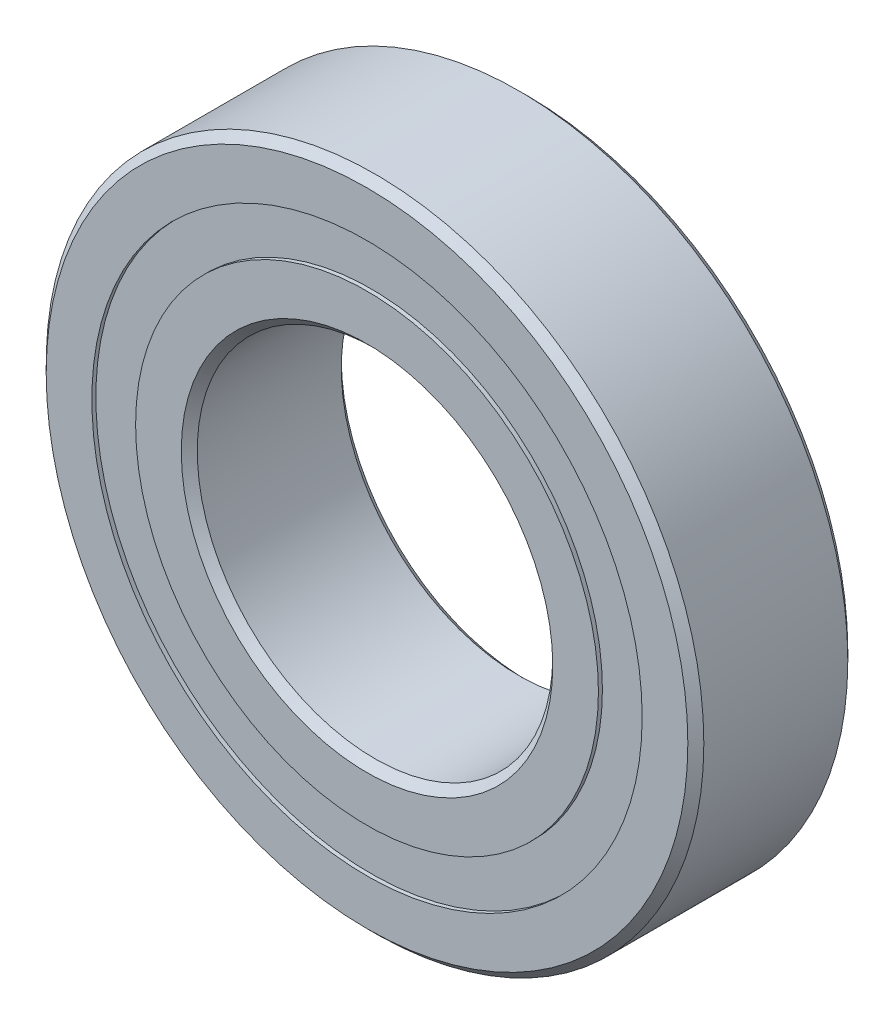
SolidWorks part; units mm, degrees
ref_plane "Front Plane" through (0, 0, 0) normal (0, 0, 1) x (1, 0, 0)
ref_plane "Top Plane" through (0, 0, 0) normal (0, 1, 0) x (1, 0, 0)
ref_plane "Right Plane" through (0, 0, 0) normal (1, 0, 0) x (0, 0, -1)
sketch "Sketch1" plane through (0, 0, 0) normal (1, 0, 0) x (0, 0, -1)
  line L0 (-4.5, 0) -> (4.5, 0) construction
  line L1 (0, 18.5) -> (0, -18.5) construction
  line L2 (4.05, 18.5) -> (-4.05, 18.5)
  line L3 (-4.05, 18.5) -> (-4.5, 18.05)
  line L4 (-4.5, 18.05) -> (-4.5, 15.4808)
  line L5 (-4.5, 15.4808) -> (-2, 15.4808)
  line L6 (4.5, 15.4808) -> (2, 15.4808)
  line L7 (4.5, 18.05) -> (4.5, 15.4808)
  line L8 (4.05, 18.5) -> (4.5, 18.05)
  line L9 (0, 18.5) -> (0, 14.25) construction
  line L10 (0, 14.25) -> (0, 10) construction
  arc A0 (-2, 15.4808) -> (2, 15.4808) centre (0, 14.25) cw
  point P14 (0, 10)
  dimension "Width" = 9
  dimension "OD" = 37
  dimension "D1" = 45
  dimension "D2" = 0.45
  dimension "Shaft Dia" = 20
  dimension "D3" = 4
  dimension "D4" = 1.2308
revolve "Revolve1" add sketch "Sketch1" angle 360 about L0
sketch "Sketch3" plane through (0, 0, 0) normal (1, 0, 0) x (0, 0, -1)
  line L0 (-4.5, 13.0192) -> (-2, 13.0192)
  line L1 (0, 18.5) -> (0, -18.5) construction
  line L2 (-4.5, 18.05) -> (-4.5, 15.4808) construction
  line L3 (-4.5, 13.0192) -> (-4.5, 10.45)
  line L4 (-4.05, 18.5) -> (-4.5, 18.05) construction
  line L5 (-4.5, 10.45) -> (-4.05, 10)
  line L6 (-4.05, 10) -> (4.05, 10)
  line L7 (4.05, 18.5) -> (4.05, -18.5) construction
  line L8 (4.05, 10) -> (4.5, 10.45)
  line L9 (4.5, -18.05) -> (4.5, 18.05) construction
  line L10 (4.5, 10.45) -> (4.5, 13.0192)
  line L11 (4.5, 13.0192) -> (2, 13.0192)
  line L13 (4.05, 18.5) -> (4.5, 18.05) construction
  arc A0 (2, 15.4808) -> (-2, 15.4808) centre (0, 14.25) ccw construction
  arc A1 (2, 13.0192) -> (-2, 13.0192) centre (0, 14.25) cw
revolve "Revolve3" add sketch "Sketch3" angle 360 about L0
sketch "Sketch4" plane through (0, 0, 0) normal (1, 0, 0) x (0, 0, -1)
  line L0 (-2.3484, 14.25) -> (2.3484, 14.25)
  arc A2 (-2.3484, 14.25) -> (2.3484, 14.25) centre (0, 14.25) cw
  arc A3 (2, 15.4808) -> (-2, 15.4808) centre (0, 14.25) ccw construction
revolve "Revolve4" add sketch "Sketch4" angle 360 about L0
ref_axis "Axis1" through (0, 0, -4.5) along (0, 0, 1)
pattern_circular "CirPattern1" count 12 every 30 about axis through (0, 0, -4.5) along (0, 0, 1) of bodies 104
sketch "Sketch5" plane through (0, 0, 0) normal (1, 0, 0) x (0, 0, -1)
  line L0 (-4.5, 15.4808) -> (-2, 15.4808) construction
  line L1 (-4.275, 15.4808) -> (-2.3484, 15.4808)
  line L2 (-4.275, 15.4808) -> (-4.275, 13.0192)
  line L3 (-4.275, 13.0192) -> (-2.3484, 13.0192)
  line L4 (-2.3484, 15.4808) -> (-2.3484, 13.0192)
  line L5 (-4.5, 13.0192) -> (-2, 13.0192) construction
  line L6 (4.5, 15.4808) -> (2, 15.4808) construction
  line L7 (4.275, 15.4808) -> (2.3484, 15.4808)
  line L8 (4.275, 15.4808) -> (4.275, 13.0192)
  line L9 (4.275, 13.0192) -> (2.3484, 13.0192)
  line L10 (2.3484, 15.4808) -> (2.3484, 13.0192)
  line L11 (4.5, 13.0192) -> (2, 13.0192) construction
  line L12 (-4.05, 18.5) -> (-4.5, 18.05) construction
  point P18 (-4.275, 18.275)
revolve "Revolve5" add sketch "Sketch5" angle 360 about L0
equation "\"D2@Sketch1\" = \"Width@Sketch1\"*.05"
equation "\"D3@Sketch1\" = \"Width@Sketch1\"/2.25"
equation "\"D4@Sketch1\" = (((\"OD@Sketch1\"-\"Width@Sketch1\")/2)/3.25)/3.5"
equation "\"D2@CirPattern1\" = 360/\"Balls@CirPattern1\""
